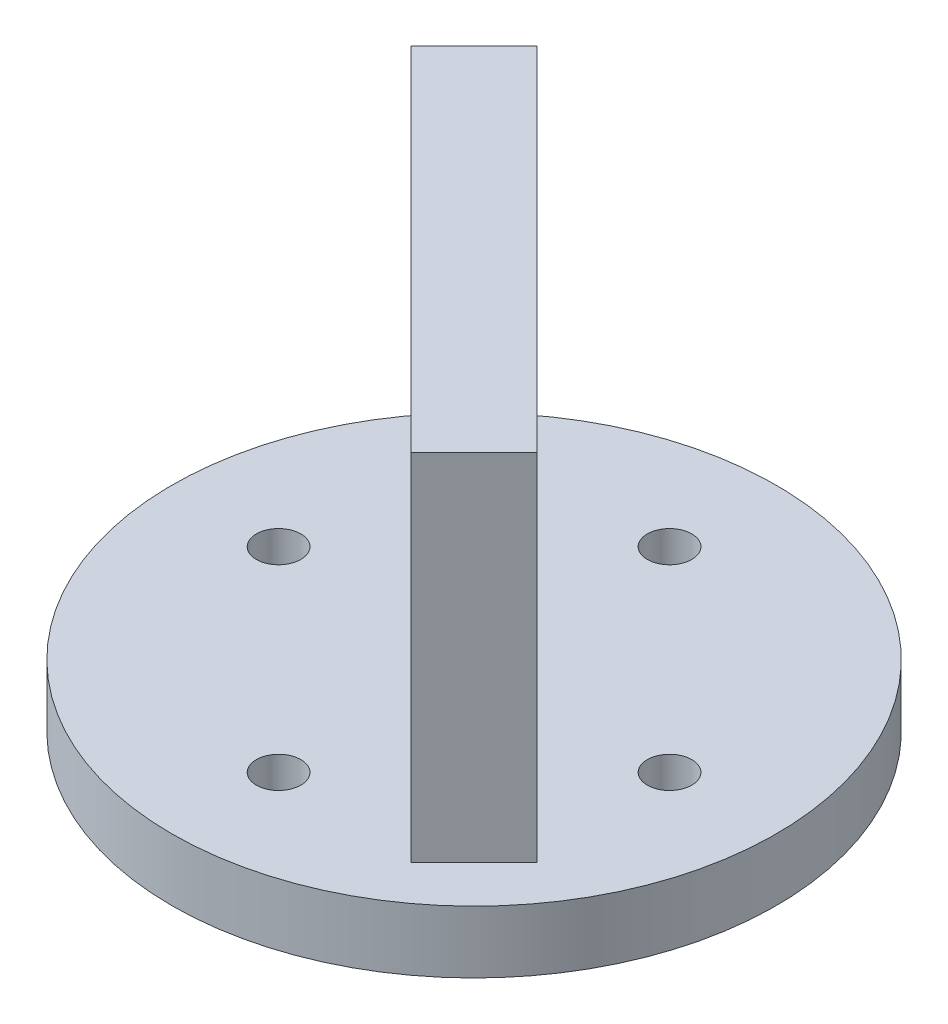
SolidWorks part; units mm, degrees
ref_plane "前视基准面" through (0, 0, 0) normal (0, 0, 1) x (1, 0, 0)
ref_plane "上视基准面" through (0, 0, 0) normal (0, 1, 0) x (1, 0, 0)
ref_plane "右视基准面" through (0, 0, 0) normal (1, 0, 0) x (0, 0, -1)
sketch "草图1" plane through (0, 0, 0) normal (0, 1, 0) x (1, 0, 0)
  circle A0 centre (0, 0) radius 34
extrude "凸台-拉伸1" add sketch "草图1" along normal blind 7
sketch "草图2" plane through (0, 7, 0) normal (0, 1, 0) x (1, 0, 0)
  circle A0 centre (22, 0) radius 2.5
  circle A1 centre (0, -22) radius 2.5
  circle A2 centre (-22, 0) radius 2.5
  circle A3 centre (0, 22) radius 2.5
  point P11 (0, 0)
  dimension "D1" = 4
extrude "切除-拉伸1" cut sketch "草图2" against normal blind 7
sketch "草图3" plane through (0, 7, 0) normal (0, 1, 0) x (1, 0, 0)
  line L0 (0, 0) -> (19.799, -19.799)
  line L1 (0, 0) -> (-19.799, 19.799)
  line L2 (-19.799, 19.799) -> (-16.2635, 23.3345)
  line L3 (19.799, -19.799) -> (16.2635, -23.3345)
  line L4 (-16.2635, 23.3345) -> (23.3345, -16.2635)
  line L5 (23.3345, -16.2635) -> (19.799, -19.799)
  line L6 (16.2635, -23.3345) -> (-23.3345, 16.2635)
  line L7 (-23.3345, 16.2635) -> (-19.799, 19.799)
extrude "凸台-拉伸2" add sketch "草图3" along normal blind 40 contours L7 L6 L3 L0 L1 | L5 L4 L2 L1 L0 region at (1.7678, 7, -1.7678) region at (-1.7678, 7, 1.7678)
